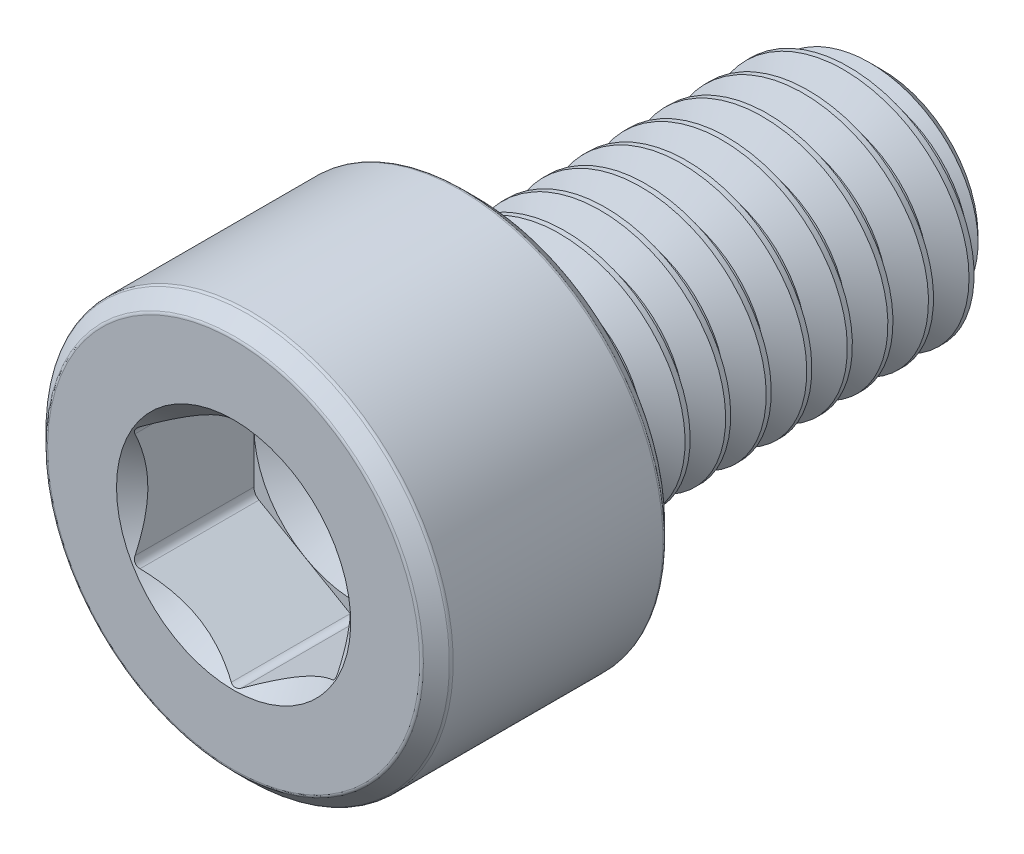
SolidWorks part; units mm, degrees
ref_plane "Front Plane" through (0, 0, 0) normal (0, 0, 1) x (1, 0, 0)
ref_plane "Top Plane" through (0, 0, 0) normal (0, 1, 0) x (1, 0, 0)
ref_plane "Right Plane" through (0, 0, 0) normal (1, 0, 0) x (0, 0, -1)
sketch "Sketch1" plane through (0, 0, 0) normal (1, 0, 0) x (0, 0, -1)
  line L0 (-8, 0) -> (8, 0) construction
  line L1 (-8, 0) -> (-8, 5)
  line L2 (-8, 5) -> (-2, 5)
  line L3 (-2, 5) -> (-2, 3)
  line L4 (-2, 3) -> (7.3505, 3)
  line L5 (7.9375, 3.1083) -> (8.4375, 2.2422) construction
  line L6 (8.4375, 2.2422) -> (8.9375, 3.1083) construction
  line L7 (8.9375, 3.1083) -> (7.9375, 3.1083) construction
  line L8 (7.3505, 3) -> (8, 2.3505)
  line L9 (8, 2.3505) -> (8, 0)
  line L10 (8, 3) -> (8.875, 3) construction
  line L11 (8.4375, 3.1083) -> (8.4375, 3) construction
  line L12 (8.4375, 3) -> (8.4375, 2.3505) construction
  line L13 (8.4375, 2.3505) -> (8.4375, 2.2422) construction
  line L14 (8.375, 2.3505) -> (8.5, 2.3505)
  line L15 (7.9688, 3.0541) -> (8.9062, 3.0541)
  line L16 (8.5, 2.3505) -> (8.9062, 3.0541)
  line L17 (8.375, 2.3505) -> (7.9688, 3.0541)
  line L18 (-8, 2.5) -> (-5, 2.5)
  line L19 (-5, 2.5) -> (-5, 0)
  line L20 (4.5, 3) -> (4.5, -3) construction
  point P20 (8.4375, 3.0541)
  point P22 (4.5, -3)
  point P28 (4.5, 0)
  point P29 (7.3505, -3)
  dimension "Head Diameter" = 10
  dimension "Length" = 10
  dimension "Head Height" = 6
  dimension "Thread Size" = 6
  dimension "D1" = 45
  dimension "Thread Pitch" = 1
  dimension "D3" = 0.125
  dimension "Drive Size" = 5
  dimension "D4" = 3.5
  dimension "D5" = 3
sketch "Sketch3" plane through (0, 0, 0) normal (1, 0, 0) x (0, 0, -1)
  line L0 (-8, 4.5862) -> (-8, 2.5)
  line L1 (-8, 2.5) -> (-5, 2.5)
  line L2 (-5, 2.5) -> (-5, 0)
  line L3 (-5, 0) -> (8, 0)
  line L4 (8, 0) -> (8, 2.3505)
  line L5 (8, 2.3505) -> (7.3505, 3)
  line L6 (7.3505, 3) -> (-2, 3)
  line L7 (-2, 3) -> (-2, 4.5862)
  line L8 (-2.4138, 5) -> (-7.5862, 5)
  line L9 (-7.9725, 4.6525) -> (-7.6525, 4.9725)
  line L11 (-8, 5) -> (-2, 5) construction
  line L12 (-2.3475, 4.9725) -> (-2.0275, 4.6525)
  arc A5 (-2.0275, 4.6525) -> (-2, 4.5862) centre (-2.0937, 4.5862) cw
  arc A6 (-2.4138, 5) -> (-2.3475, 4.9725) centre (-2.4138, 4.9063) cw
  arc A7 (-7.5862, 5) -> (-7.6525, 4.9725) centre (-7.5862, 4.9063) ccw
  arc A8 (-8, 4.5862) -> (-7.9725, 4.6525) centre (-7.9062, 4.5862) cw
  point P17 (-5, 5)
  point P29 (-8, 4.625)
  dimension "D1" = 45
  dimension "D3" = 0.0938
  dimension "D2" = 0.375
revolve "Revolve1" add sketch "Sketch3" angle 360 about L0
sketch "Sketch4" plane through (0, 0, 8) normal (0, 0, 1) x (1, 0, 0)
  line L1 (0, 2.8868) -> (-2.5, 1.4434)
  line L2 (-2.5, 1.4434) -> (-2.5, -1.4434)
  line L3 (-2.5, -1.4434) -> (0, -2.8868)
  line L4 (0, -2.8868) -> (2.5, -1.4434)
  line L5 (2.5, -1.4434) -> (2.5, 1.4434)
  line L6 (2.5, 1.4434) -> (0, 2.8868)
  circle A0 centre (0, 0) radius 2.5 construction
extrude "Cut-Extrude1" cut sketch "Sketch4" against normal up to vertex (3 mm away) up to point (0, 2.5, 5)
sketch "Sketch5" plane through (0, 0, 8) normal (0, 0, 1) x (1, 0, 0)
  circle A0 centre (0, 0) radius 2.8868
extrude "Cut-Extrude2" cut sketch "Sketch5" against normal up to next (3 mm away) draft 45
sketch "Sketch10" plane through (0, 0, 5) normal (0, 0, 1) x (1, 0, 0)
  line L0 (2.5, 1.4434) -> (2.5, -1.4434) construction
  circle A0 centre (0, 0) radius 2.5
extrude "Cut-Extrude3" cut sketch "Sketch10" against normal through all draft 60
fillet "Fillet1" radius 0.25 6 edges at (-2.5, 1.4434, 6.5) (0, 2.8868, 6.5) (2.5, 1.4434, 6.5) (2.5, -1.4434, 6.5) (0, -2.8868, 6.5) (-2.5, -1.4434, 6.5)
sketch "Sketch6" plane through (0, 0, -8) normal (0, 0, -1) x (-1, 0, 0)
  circle A0 centre (0, 0) radius 3 construction
  circle A1 centre (0, 0) radius 3
curve "Helix/Spiral1" pitch 1 height 11 radius 3 centre (0, 0, -8) axis (0, 0, 1) start towards (0, 1, 0)
sketch "Sketch7" plane through (0, 0, 0) normal (1, 0, 0) x (0, 0, -1)
  line L0 (8.375, 2.3505) -> (8.5, 2.3505) construction
  line L1 (8.375, 2.3505) -> (7.9688, 3.0541) construction
  line L2 (7.9688, 3.0541) -> (8.9062, 3.0541) construction
  line L3 (8.5, 2.3505) -> (8.9062, 3.0541) construction
  line L4 (8.375, 2.3505) -> (8.5, 2.3505)
  line L5 (8.375, 2.3505) -> (7.9688, 3.0541)
  line L6 (7.9688, 3.0541) -> (8.9062, 3.0541)
  line L7 (8.5, 2.3505) -> (8.9062, 3.0541)
sweep "Cut-Sweep1" cut profiles "Sketch7" path "Helix/Spiral1" align with end faces yes
sketch "Sketch11" plane through (0, 0, 0) normal (1, 0, 0) x (0, 0, -1)
  line L0 (-2, 3.25) -> (-1.75, 3) construction
  line L1 (-2, 5) -> (-2, 3) construction
  line L2 (-2, 3) -> (7.3505, 3) construction
  line L3 (-1.75, 3) -> (-1.5, 3)
  line L4 (-1.5, 3) -> (1.5, 0)
  line L5 (-8, 0) -> (8, 0) construction
  line L6 (1.5, 0) -> (-2, 0)
  line L7 (-2, 0) -> (-2, 3.25) construction
  line L8 (-2, 3.25) -> (-3.5566, 3.25)
  line L9 (-3.5566, 3.25) -> (-3.5566, 0)
  line L10 (-3.5566, 0) -> (-2, 0)
  arc A0 (-1.75, 3) -> (-2, 3.25) centre (-1.75, 3.25) cw
  dimension "D1" = 45
  dimension "D2" = 0.25
  dimension "D3" = 45
  dimension "D4" = 0.5
revolve "Revolve2" add sketch "Sketch11" angle 360 about L6
equation "\"D3@Sketch1\" = \"Thread Pitch@Sketch1\" / 8"
equation "\"D4@Sketch1\" = \"Thread Pitch@Sketch1\" * 3.5"
equation "\"D3@Helix/Spiral1\" = \"Length@Sketch1\" + \"Thread Pitch@Sketch1\""
equation "\"D4@Helix/Spiral1\" = \"Thread Pitch@Sketch1\""
equation "\"D5@Sketch1\"=\"Head Height@Sketch1\"*0.5"
equation "\"D2@Sketch3\"=\"Head Diameter@Sketch1\" *0.0375"
equation "\"D2@Sketch11\"=\"Thread Pitch@Sketch1\" / 4"
equation "\"D4@Sketch11\"=\"Thread Pitch@Sketch1\"/2"
equation "\"D1@Fillet1\"=\"Drive Size@Sketch1\"*0.05"
equation "\"D1@Fillet1\" = \"Drive Size@Sketch1\" * 0.05"
equation "\"D3@Sketch3\"=\"D2@Sketch3\"*0.25"
